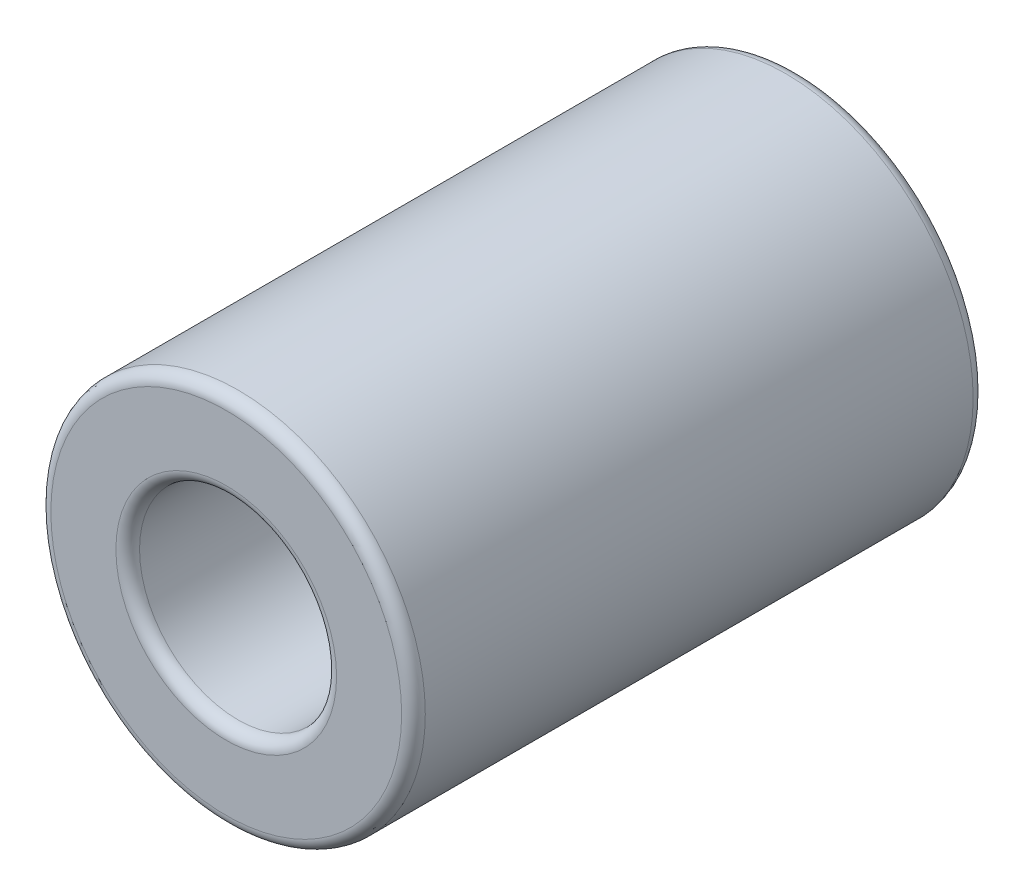
SolidWorks part; units mm, degrees
ref_plane "Plan de face" through (0, 0, 0) normal (0, 0, 1) x (1, 0, 0)
ref_plane "Plan de dessus" through (0, 0, 0) normal (0, 1, 0) x (1, 0, 0)
ref_plane "Plan de droite" through (0, 0, 0) normal (1, 0, 0) x (0, 0, -1)
sketch "Esquisse1" plane through (0, 0, 0) normal (0, 0, 1) x (1, 0, 0)
  circle A0 centre (0, 0) radius 5
  circle A1 centre (0, 0) radius 9.5
  dimension "D1" = 10
  dimension "D2" = 19
extrude "Boss.-Extru.1" add sketch "Esquisse1" along normal blind 29
fillet "Congé1" radius 0.6 4 edges at (5, 0, 29) (5, 0, 0) (9.5, 0, 0) (9.5, 0, 29)
